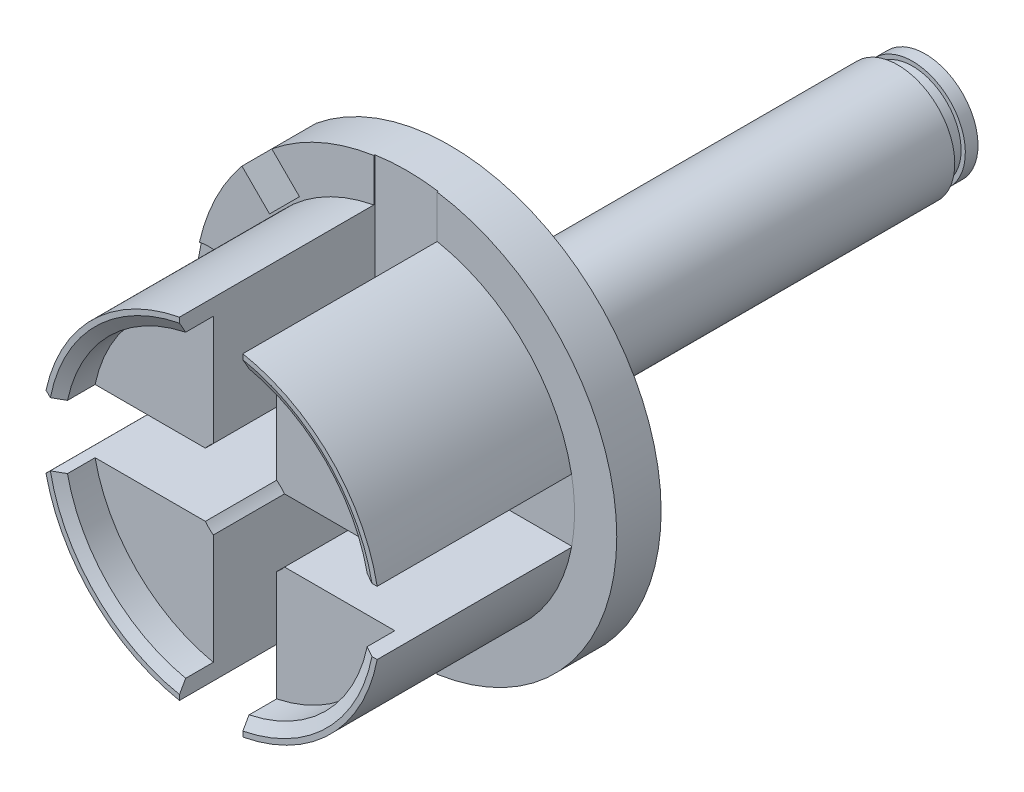
SolidWorks part; units mm, degrees
ref_plane "Front Plane" through (0, 0, 0) normal (0, 0, 1) x (1, 0, 0)
ref_plane "Top Plane" through (0, 0, 0) normal (0, 1, 0) x (1, 0, 0)
ref_plane "Right Plane" through (0, 0, 0) normal (1, 0, 0) x (0, 0, -1)
sketch "Sketch1" plane through (0, 0, 0) normal (0, 0, 1) x (1, 0, 0)
  circle A0 centre (0, 0) radius 10
  dimension "D1" = 20
extrude "Boss-Extrude1" add sketch "Sketch1" against normal blind 2.05
sketch "Sketch2" plane through (0, 0, -2.05) normal (0, 0, -1) x (-1, 0, 0)
  circle A0 centre (0, 0) radius 2.7
  dimension "D1" = 5.4
extrude "Boss-Extrude2" add sketch "Sketch2" along normal blind 22.5
sketch "Sketch3" plane through (0, 0, 0) normal (1, 0, 0) x (0, 0, -1)
  line L0 (0, 0) -> (24.55, 0) construction
  line L1 (24.55, -2.7) -> (24.55, 2.7) construction
  line L2 (24.55, 2.7) -> (2.05, 2.7) construction
  line L3 (2.05, 2.7) -> (2.85, 2.7)
  line L4 (2.05, 2.7) -> (2.05, 2.6)
  line L5 (2.05, 2.6) -> (2.85, 2.6)
  line L6 (2.85, 2.7) -> (2.85, 2.6)
  line L7 (2.05, -10) -> (2.05, 10) construction
  dimension "D1" = 0.8
  dimension "D2" = 5.2
revolve "Cut-Revolve1" cut sketch "Sketch3" angle 360 about L0
sketch "Sketch4" plane through (0, 0, 0) normal (1, 0, 0) x (0, 0, -1)
  line L0 (0, 0) -> (24.55, 0) construction
  line L1 (24.55, -2.7) -> (24.55, 2.7) construction
  line L2 (24.55, 2.7) -> (2.85, 2.7) construction
  line L4 (23.25, 2.7) -> (23.25, 2.3)
  line L5 (23.25, 2.3) -> (23.95, 2.3)
  line L6 (23.95, 2.5) -> (23.95, 2.3)
  line L7 (23.95, 2.5) -> (24.55, 2.5)
  line L8 (2.05, -10) -> (2.05, 10) construction
  line L9 (24.55, 2.7) -> (23.25, 2.7)
  line L11 (24.55, 2.7) -> (24.55, 2.5)
  dimension "D1" = 4.6
  dimension "D2" = 0.7
  dimension "D3" = 21.9
  dimension "D4" = 5
revolve "Cut-Revolve2" cut sketch "Sketch4" angle 360 about L0
sketch "Sketch5" plane through (0, 0, 0) normal (0, 0, 1) x (1, 0, 0)
  line L0 (0, 10) -> (0, -10) construction
  line L1 (-1.5, 9.8869) -> (-1.5, 7.8581)
  line L2 (1.5, 9.8869) -> (1.5, 7.8581)
  line L3 (-1.5, -7.8581) -> (-1.5, -9.8869)
  line L4 (-1.5, 10) -> (-1.5, -10) construction
  line L5 (1.5, 10) -> (1.5, -10) construction
  line L6 (1.5, -7.8581) -> (1.5, -9.8869)
  arc A0 (-1.5, 7.8581) -> (-1.5, -7.8581) centre (0, 0) ccw
  arc A1 (1.5, -7.8581) -> (1.5, 7.8581) centre (0, 0) ccw
  circle A2 centre (0, 0) radius 10 construction
  arc A3 (-1.5, 9.8869) -> (-1.5, -9.8869) centre (0, 0) ccw
  arc A4 (1.5, -9.8869) -> (1.5, 9.8869) centre (0, 0) ccw
  dimension "D1" = 16
  dimension "D3" = 1.5
  dimension "D4" = 1.5
extrude "Boss-Extrude3" add sketch "Sketch5" along normal offset from surface (0.05 mm away) 2.1 up to face at (10, 0, -2.05)
sketch "Sketch6" plane through (0, 0, 0) normal (0, 0, 1) x (1, 0, 0)
  line L0 (0, 10) -> (0, -10) construction
  line L1 (-10, 0) -> (10, 0) construction
  line L3 (-7.8581, 1.5) -> (-1.5, 1.5)
  line L4 (-1.5, 7.8581) -> (-1.5, 9.8869) construction
  line L5 (-1.5, 1.5) -> (-1.5, 7.8581)
  line L6 (-10, 1.5) -> (10, 1.5) construction
  arc A0 (-1.5, 7.8581) -> (-7.8581, 1.5) centre (0, 0) ccw
  arc A1 (-1.5, 7.8581) -> (-1.5, -7.8581) centre (0, 0) ccw construction
  arc A2 (1.5, 9.8869) -> (-1.5, 9.8869) centre (0, 0) ccw construction
  arc A3 (-1.5, -9.8869) -> (1.5, -9.8869) centre (0, 0) ccw construction
  arc A4 (-1.5, 9.8869) -> (-1.5, -9.8869) centre (0, 0) ccw construction
  arc A5 (1.5, -9.8869) -> (1.5, 9.8869) centre (0, 0) ccw construction
  dimension "D2" = 1.5
extrude "Boss-Extrude4" add sketch "Sketch6" along normal offset from surface (9.25 mm away) 9.2 up to face at (-5.25, 0, 0.05) offset beyond the face yes
pattern_circular "CirPattern6" count 4 over 360 about axis through (0, 0, 27.4417) along (0, 0, -1) of "Boss-Extrude4"
sketch "Sketch19" plane through (0, 0, 0) normal (1, 0, 0) x (0, 0, -1)
  line L0 (-0.05, 8) -> (-0.05, 8.6866)
  line L1 (-0.05, 9.8869) -> (-0.05, -9.8869) construction
  line L4 (-0.05, 8.6866) -> (0.1732, 8.3)
  line L5 (-0.05, 8) -> (0, 8)
  line L6 (-9.25, 7.8581) -> (-0.05, 7.8581) construction
  line L8 (0, 0) -> (-10.5242, 0) construction
  line L9 (-9.25, 0) -> (-0.05, 0) construction
  line L10 (-0.05, 7.8581) -> (-0.05, 9.8869) construction
  arc A0 (0, 8) -> (0.1732, 8.3) centre (0, 8.2) ccw
  dimension "D2" = 0.2
  dimension "D1" = 60
  dimension "D3" = 0.25
  dimension "D4" = 16
revolve "Cut-Revolve5" [suppressed] cut sketch "Sketch19" angle 360 about L8
sketch "Sketch8" plane through (0, 0, 0) normal (1, 0, 0) x (0, 0, -1)
  line L0 (0, 0) -> (-12.1697, 0) construction
  line L1 (-9.25, 0) -> (-0.05, 0) construction
  line L2 (-9.25, 7.7581) -> (-8.9566, 7.25)
  line L3 (-9.25, 7.8581) -> (-9.25, 1.5) construction
  line L4 (-8.9566, 7.25) -> (-7.65, 7.25)
  line L5 (-7.65, 7.25) -> (-7.65, 0)
  line L6 (2.05, -10) -> (2.05, 10) construction
  line L7 (-9.25, 7.7581) -> (-9.25, 0)
  line L8 (-9.25, 0) -> (-7.65, 0)
  dimension "D1" = 9.7
  dimension "D2" = 0.1
  dimension "D3" = 30
  dimension "D4" = 14.5
revolve "Cut-Revolve3" cut sketch "Sketch8" angle 360 about L0
sketch "Sketch9" plane through (0, 0, -24.55) normal (0, 0, -1) x (-1, 0, 0)
  circle A0 centre (0, 0) radius 1.5
  dimension "D1" = 3
extrude "Cut-Extrude1" cut sketch "Sketch9" against normal through all
hole_wizard "Ø4.8 (4.8) Diameter Hole1" positions "Sketch12" profile "Sketch11" hole size "Ø4.8" standard "DIN"
sketch "Sketch12" plane through (0, 0, 9.25) normal (0, 0, 1) x (1, 0, 0)
  point P0 (0, 0)
sketch "Sketch11" plane through (0, 0, 9.25) normal (1, 0, 0) x (0, -1, 0)
  line L0 (0, 0) -> (0, 10.8421)
  line L1 (0, 10.8421) -> (2.4, 9.4)
  line L2 (2.4, 9.4) -> (2.4, 0)
  line L5 (2.4, 0) -> (0, 0)
  line L10 (0, 10.8421) -> (-2.4, 9.4) construction
  line L11 (0, -6.35) -> (0, 107.95) construction
  dimension "Hole Dia." = 4.8
  dimension "Hole Depth" = 9.4
  dimension "Drill Angle" = 118
sketch "Sketch13" plane through (0, 0, 9.25) normal (0, 0, 1) x (1, 0, 0)
  line L0 (-7.8581, 1.5) -> (-7.6117, 1.5) construction
  circle A0 centre (-9.2949, 0) radius 2.25
  arc A1 (-1.5, 7.8581) -> (-7.8581, 1.5) centre (0, 0) ccw construction
  point P2 (-7.6179, 1.5)
  point P4 (-7.8179, 1.6973)
  dimension "D1" = 4.5
  dimension "D2" = 0.2
extrude "Cut-Extrude2" cut sketch "Sketch13" against normal offset from surface (9.3 mm away) 2 up to face at (10, 0, -2.05)
sketch "Sketch14" plane through (0, 0, 0.05) normal (0, 0, 1) x (1, 0, 0)
  line L0 (0, 0) -> (-10, 0) construction
  line L1 (0, 0) -> (-8.1267, 8.1267) construction
  line L2 (-5.0205, 6.4347) -> (-6.3285, 7.7427)
  line L4 (-5.0205, 6.4347) -> (-6.4347, 5.0205)
  line L5 (-6.4347, 5.0205) -> (-7.7427, 6.3285)
  line L7 (0.7071, 0.7071) -> (-7.4196, 8.8338) construction
  arc A0 (-9.7544, 2.2026) -> (-9.7544, -2.2026) centre (0, 0) ccw construction
  arc A1 (-1.5, 9.8869) -> (-9.7544, 2.2026) centre (0, 0) ccw construction
  arc A2 (-6.3285, 7.7427) -> (-7.7427, 6.3285) centre (0, 0) ccw
  point P9 (-1.4142, -1.4142)
  point P10 (-9.5409, 6.7125)
  dimension "D1" = 45
  dimension "D4" = 8.1
  dimension "D2" = 2
extrude "Cut-Extrude3" cut sketch "Sketch14" against normal up to next
sketch "Sketch15" plane through (0, 0, 0) normal (1, 0, 0) x (0, 0, -1)
  line L0 (0, 0) -> (25.1642, 0) construction
  line L1 (24.55, 0) -> (23.95, 0) construction
  line L2 (2.05, 0) -> (-0.05, 0) construction
  line L3 (24.55, -2.5) -> (24.55, 2.5) construction
  line L4 (5.55, 0) -> (18.55, 0)
  line L5 (5.55, 0) -> (5.55, 1.7)
  line L6 (5.55, 1.7) -> (18.55, 1.7)
  line L7 (18.55, 0) -> (18.55, 1.7)
  dimension "D1" = 6
  dimension "D2" = 13
  dimension "D3" = 3.4
revolve "Cut-Revolve4" cut sketch "Sketch15" angle 360 about L0
hole_wizard "M1.4x0.3 Tapped Hole1" positions "Sketch17" profile "Sketch18" tap size "M1.4x0.3" standard "ANSI Metric" end condition up to next
sketch "Sketch17" plane through (0, 0, 0) normal (0, 0, 1) x (1, 0, 0)
  circle A0 centre (0, 0) radius 3.5 construction
  point P4 (0, 3.5)
  point P6 (0, -3.5)
  dimension "D1" = 7
cosmetic thread "Hole Thread1" parameters "D2"=1.4
cosmetic thread "Hole Thread2" parameters "D2"=1.4
sketch "Sketch18" plane through (0, 3.5, 0) normal (1, 0, 0) x (0, -1, 0)
  line L0 (0, 0) -> (0, 2.05)
  line L1 (0, 2.05) -> (0.55, 2.05)
  line L2 (0.55, 2.05) -> (0.55, 0)
  line L5 (0.55, 0) -> (0, 0)
  line L11 (0, -6.35) -> (0, 107.95) construction
  dimension "Thru Tap Drill Dia." = 1.1
  dimension "Thru Tap Drill Depth" = 2.05
sketch "Sketch21" plane through (0, 0, 0) normal (1, 0, 0) x (0, 0, -1)
  line L0 (12.05, 0) -> (12.05, -3.2344) construction
  line L1 (23.25, 0) -> (2.85, 0) construction
  line L2 (2.05, -10) -> (2.05, 10) construction
  line L3 (23.25, 2.7) -> (2.85, 2.7) construction
  line L4 (12.05, -0.6967) -> (10.2888, -2.9918)
  line L5 (12.05, -0.6967) -> (12.05, -3)
  line L6 (10.2826, -3) -> (12.05, -3)
  line L9 (10.2888, -2.9918) -> (10.2826, -3)
  circle A0 centre (12.05, -2.75) radius 1.25 construction
  dimension "D2" = 2.5
  dimension "D1" = 10
  dimension "D3" = 6.7
  dimension "D4" = 37.5
  dimension "D5" = 3
revolve "Cut-Revolve6" cut sketch "Sketch21" angle 360 about L0
